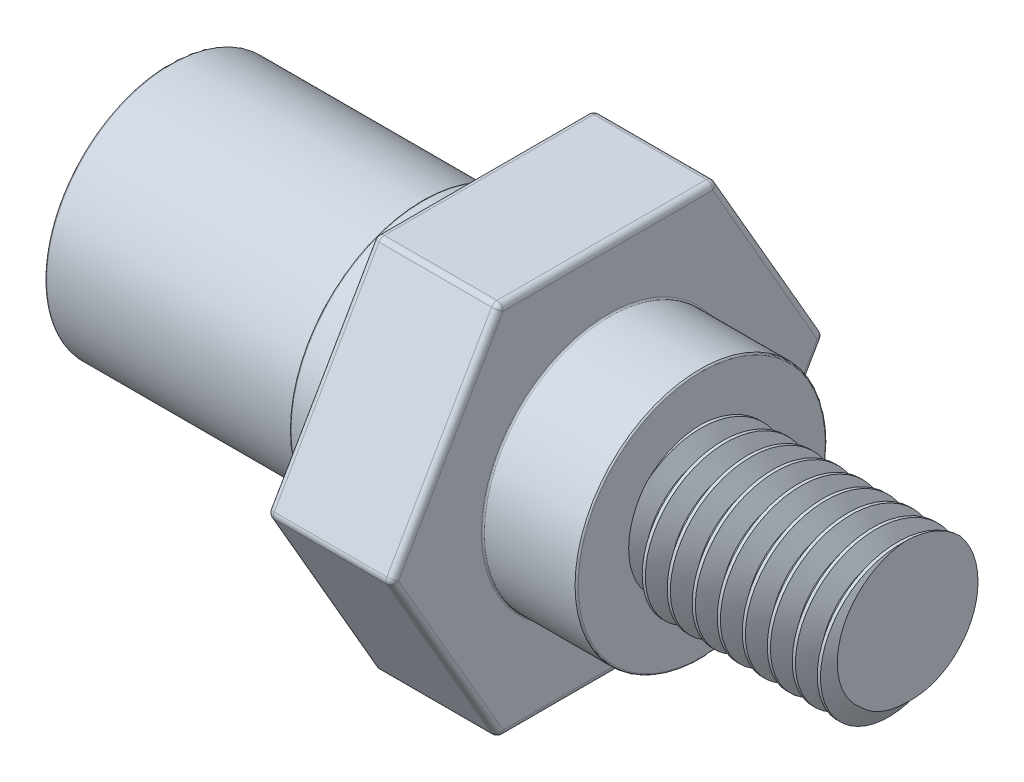
SolidWorks part; units mm, degrees
note: The reader was unsure of these and kept them because the rebuilt part matched: shared geometry of "Sketch1<4>", "Sketch1<2>", "Sketch1<5>", "Sketch1<6>".
ref_plane "Front Plane" through (0, 0, 0) normal (0, 0, 1) x (1, 0, 0)
ref_plane "Top Plane" through (0, 0, 0) normal (0, 1, 0) x (1, 0, 0)
ref_plane "Right Plane" through (0, 0, 0) normal (1, 0, 0) x (0, 0, -1)
sketch "Sketch1" plane through (0, 0, 0) normal (1, 0, 0) x (0, 0, -1)
  line L1 (6.9282, 0) -> (3.4641, 6)
  line L2 (3.4641, 6) -> (-3.4641, 6)
  line L3 (-3.4641, 6) -> (-6.9282, 0)
  line L4 (-6.9282, 0) -> (-3.4641, -6)
  line L5 (-3.4641, -6) -> (3.4641, -6)
  line L6 (3.4641, -6) -> (6.9282, 0)
  circle A0 centre (0, 0) radius 6 construction
  circle A1 centre (0, 0) radius 4
  circle A2 centre (0, 0) radius 2.5
  circle A3 centre (0, 0) radius 3
  circle A4 centre (0, 0) radius 4.25
  dimension "D2" = 8
  dimension "D3" = 5
  dimension "D4" = 6
  dimension "D5" = 8.5
  dimension "D1" = 12
extrude "Boss-Extrude1" add sketch "Sketch1" along normal blind 4 contours L5 L6 L1 L2 L3 L4 A1 | A1 A3 | A3 A2 | A4 A1
extrude "Boss-Extrude3" add sketch "Sketch1<4>" along normal blind 13.5 contours A2
sketch "Sketch1<4>" plane through (0, 0, 0) normal (1, 0, 0) x (0, 0, -1) same geometry as "Sketch1"
sketch "Sketch2" plane through (13.5, 0, 0) normal (1, 0, 0) x (0, 0, -1)
  circle A0 centre (0, 0) radius 2
curve "Helix/Spiral1" pitch 0.8 height 7.2 turns 9
sketch "Sketch3" plane through (0, 0, 0) normal (0, 0, 1) x (1, 0, 0)
  line L0 (13.85, 2.5) -> (14.3633, 2.7829) construction
  line L1 (14.3633, 2.7829) -> (13.3367, 2.7829)
  line L2 (13.3367, 2.7829) -> (13.85, 2.5) construction
  line L3 (13.3367, 2.7829) -> (13.85, 1.8938) construction
  line L4 (13.85, 2.5) -> (13.85, 1.8938) construction
  line L5 (13.85, 1.8938) -> (14.3633, 2.7829) construction
  line L6 (13.85, 2.5) -> (13.5, 2.5) construction
  line L7 (13.5, -2.5) -> (13.5, 2.5) construction
  line L8 (13.8, 1.9804) -> (13.9, 1.9804)
  line L9 (13.3367, 2.7829) -> (13.8, 1.9804)
  line L10 (14.3633, 2.7829) -> (13.9, 1.9804)
  dimension "D1" = 60
  dimension "D2" = 0.35
  dimension "D3" = 0.1
sweep "Cut-Sweep1" cut profiles "Sketch3" path "Helix/Spiral1"
extrude "Boss-Extrude2" add sketch "Sketch1<2>" along normal blind 7 and the other way blind 10 contours A1 | A3 A2 | A2
sketch "Sketch1<2>" plane through (0, 0, 0) normal (1, 0, 0) x (0, 0, -1) same geometry as "Sketch1"
extrude "Cut-Extrude1" cut sketch "Sketch1<5>" against normal blind 21 contours A3 A2 | A2
sketch "Sketch1<5>" plane through (0, 0, 0) normal (1, 0, 0) x (0, 0, -1) same geometry as "Sketch1"
extrude "Boss-Extrude4" add sketch "Sketch1<6>" against normal blind 2 contours A4 A1
sketch "Sketch1<6>" plane through (0, 0, 0) normal (1, 0, 0) x (0, 0, -1) same geometry as "Sketch1"
sketch "Sketch4" plane through (0, 0, 0) normal (0, 0, 1) x (1, 0, 0)
  line L0 (-14.4033, 0) -> (18.7158, 0) construction
  line L1 (0, 4.8658) -> (0.2801, 7.1469)
  line L2 (0, 6) -> (0, 0) construction
  line L3 (0.2801, 7.1469) -> (-0.3159, 7.1469)
  line L4 (-0.3159, 7.1469) -> (-0.3159, 4.8658)
  line L5 (-0.3159, 4.8658) -> (0, 4.8658)
  line L6 (4, 4.8658) -> (3.7199, 7.1469)
  line L7 (4, 6) -> (4, 0) construction
  line L8 (3.7199, 7.1469) -> (4.3159, 7.1469)
  line L9 (4.3159, 7.1469) -> (4.3159, 4.8658)
  line L10 (4.3159, 4.8658) -> (4, 4.8658)
  dimension "D1" = 7
  dimension "D2" = 7
chamfer "Chamfer1" distance 0.2 angle 23 1 edges at (-2, 0, -4.25)
fillet "Fillet1" radius 0.05 6 edges at (-2, 0, -4) (-10, 0, -4) (7, 0, -4) (4, 0, -4) (0, 0, -4.25) (-1.9151, 0, -4.25)
fillet "Fillet2" radius 0.2 18 edges at (2, 0, -6.9282) (2, 6, -3.4641) (2, 6, 3.4641) (2, 0, 6.9282) (2, -6, -3.4641) (2, -6, 3.4641) (4, -3, -5.1962) (0, -3, -5.1962) (4, 3, -5.1962) (0, 3, -5.1962) (4, 6, 0) (0, 6, 0) (4, 3, 5.1962) (0, 3, 5.1962) (4, -3, 5.1962) (0, -3, 5.1962) (4, -6, 0) (0, -6, 0)
